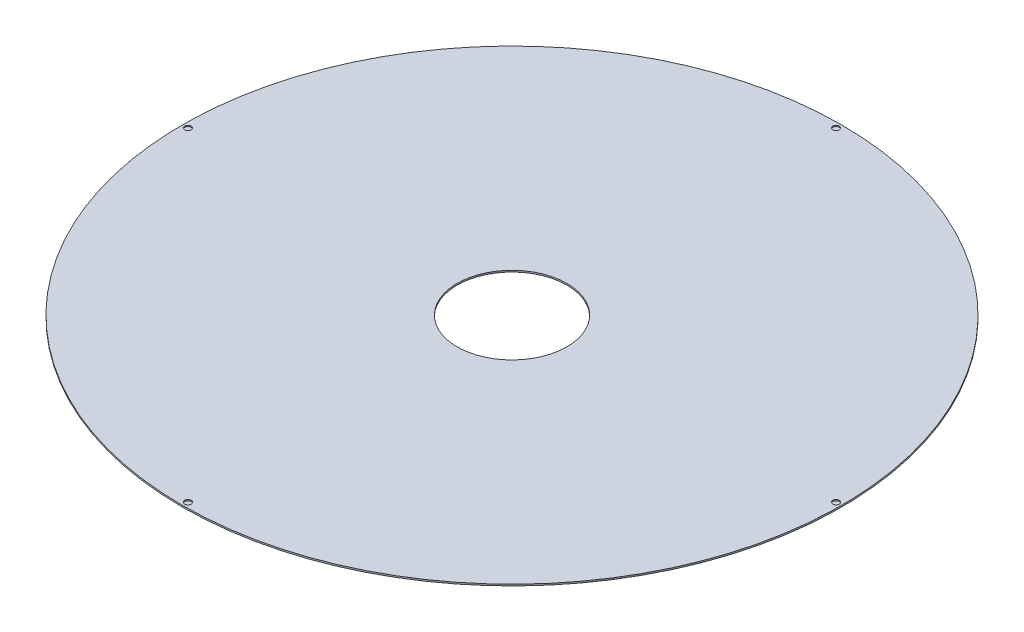
SolidWorks part; units mm, degrees
material "AISI 1020"
ref_plane "Front Plane" through (0, 0, 0) normal (0, 0, 1) x (1, 0, 0)
ref_plane "Top Plane" through (0, 0, 0) normal (0, 1, 0) x (1, 0, 0)
ref_plane "Right Plane" through (0, 0, 0) normal (1, 0, 0) x (0, 0, -1)
sketch "Sketch1" plane through (0, 0, 0) normal (0, 0, 1) x (1, 0, 0)
  line L0 (0, 0) -> (0, 30.5205) construction
  line L1 (0, 0) -> (250, 0)
  line L2 (250, 3.5) -> (250, -3.5)
  line L3 (250, 3.5) -> (1500, 3.5)
  line L4 (1500, 3.5) -> (1500, -3.5)
  line L5 (1500, -3.5) -> (250, -3.5)
  point P7 (250, 0)
revolve "Revolve1" add sketch "Sketch1" angle 360 about L0
sketch "Sketch2" plane through (0, 3.5, 0) normal (0, 1, 0) x (1, 0, 0)
  line L0 (0, -1475) -> (0, 1475)
  line L1 (-1475, 0) -> (1475, 0)
  circle A6 centre (0, 1475) radius 15
  circle A8 centre (-1475, 0) radius 15
  circle A9 centre (1475, 0) radius 15
  circle A10 centre (0, -1475) radius 15
  point P2 (0, 0)
  point P7 (0, 0)
  point P8 (0, 0)
extrude "Cut-Extrude1" cut sketch "Sketch2" against normal blind 5 contours A8 | A6 | A9 | A10
